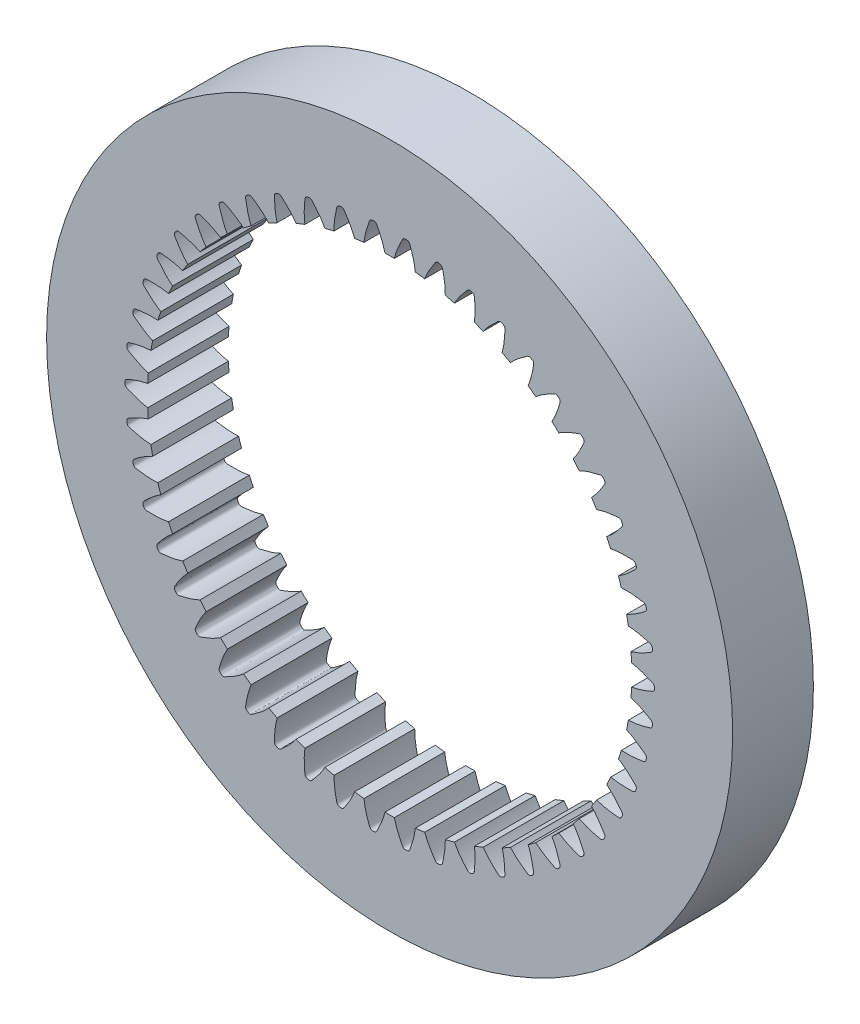
SolidWorks part; units mm, degrees
material "Д16 ГОСТ 4784-97"
ref_plane "FRONT" through (0, 0, 0) normal (0, 0, 1) x (1, 0, 0)
ref_plane "TOP" through (0, 0, 0) normal (0, 1, 0) x (1, 0, 0)
ref_plane "RIGHT" through (0, 0, 0) normal (1, 0, 0) x (0, 0, -1)
ref_axis "Ось1" through (0, 0, 50) along (0, 0, -1)
sketch "SketchRevolveSpurGear" plane through (0, 0, 0) normal (1, 0, 0) x (0, 0, -1)
  line L0 (0, 0) -> (1, 0) construction
  line L1 (-5, 24) -> (-5, 34)
  line L2 (-5, 34) -> (3, 34)
  line L3 (3, 34) -> (3, 24)
  line L4 (3, 24) -> (-5, 24)
  dimension "MinorDiameter" = 24
  dimension "D1" = 10
  dimension "D2" = 8
revolve "SpurGear" add sketch "SketchRevolveSpurGear" angle 360 about L0
sketch "SketchToothSpurGear" plane through (0, 0, 0) normal (0, 0, 1) x (1, 0, 0)
  arc A0 (23.9478, -1.0449) -> (23.9478, 1.0449) centre (0, 0) ccw
  spline S0 degree 3 poles (23.9478, 1.0449) (24.0534, 1.0283) (24.2208, 0.9962) (24.4553, 0.9411) (24.6593, 0.8868) (24.881, 0.8208) (25.12, 0.742) (25.3754, 0.6489) (25.6481, 0.5429) (25.8932, 0.4297) (26.0712, 0.3634) (26.1495, 0.3046) (26.1792, 0.2741) (26.2044, 0.2398) (26.2245, 0.2023) (26.244, 0.1497) (26.2507, 0.0943) (26.2498, 0.04) (26.2501, 0) (26.2498, -0.04) (26.2507, -0.0943) (26.244, -0.1497) (26.2245, -0.2023) (26.2044, -0.2398) (26.1792, -0.2741) (26.1495, -0.3046) (26.0712, -0.3634) (25.8932, -0.4297) (25.6481, -0.5429) (25.3754, -0.6489) (25.12, -0.742) (24.881, -0.8208) (24.6593, -0.8868) (24.4553, -0.9411) (24.2208, -0.9962) (24.0534, -1.0283) (23.9478, -1.0449) knots 0 0 0 0 0.060157 0.095945 0.135541 0.178944 0.226153 0.277169 0.331993 0.390623 0.429646 0.437605 0.445564 0.453522 0.461481 0.46944 0.484978 0.492489 0.5 0.507511 0.515022 0.53056 0.538519 0.546478 0.554436 0.562395 0.570354 0.609377 0.668007 0.722831 0.773847 0.821056 0.864459 0.904055 0.939843 1 1 1 1
extrude "ToothExtrudeCutSpurGear" cut sketch "SketchToothSpurGear" against normal blind 5 and the other way blind 5
pattern_circular "PatternSpurGear" count 50 every 7.2 about axis through (0, 0, 50) along (0, 0, -1) of "ToothExtrudeCutSpurGear"
sketch "AuxiliarySketchSpurGear" plane through (0, 0, 0) normal (0, 0, 1) x (1, 0, 0)
  circle A0 centre (0, 0) radius 25 construction
  circle A1 centre (0, 0) radius 23.4923 construction
  circle A2 centre (0, 0) radius 26.25 construction
  circle A3 centre (0, 0) radius 24 construction
  dimension "PitchDiameter" = 50
  dimension "BaseDiameter" = 46.9846
  dimension "MajorDiameter" = 52.5
  dimension "MinorDiameter" = 48
